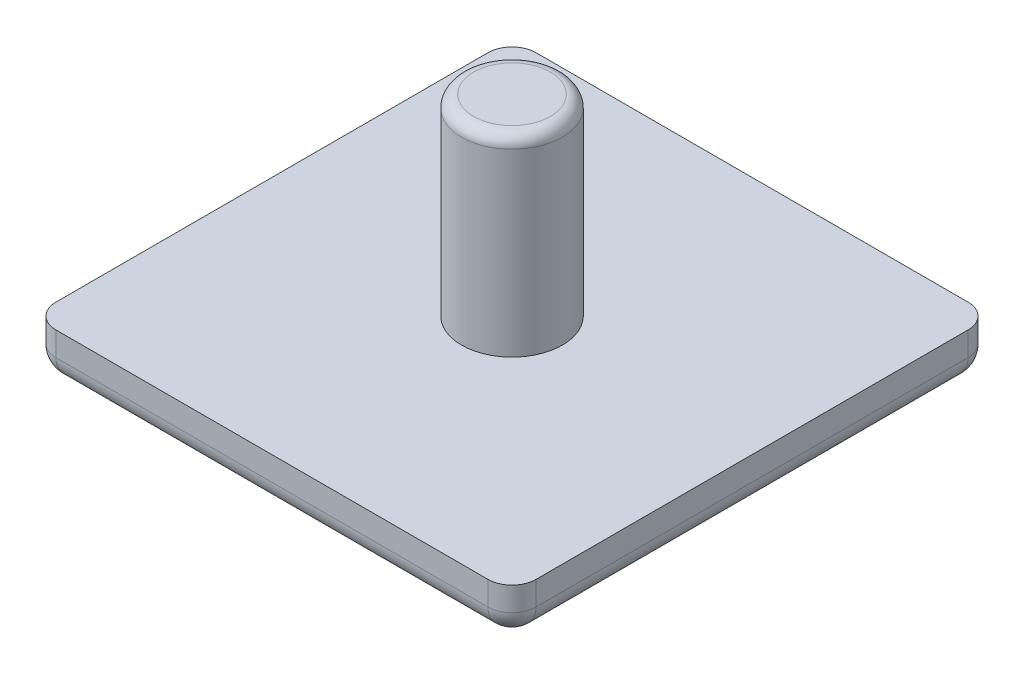
SolidWorks part; units mm, degrees
material "PVC Rigid"
ref_plane "Front Plane" through (0, 0, 0) normal (0, 0, 1) x (1, 0, 0)
ref_plane "Top Plane" through (0, 0, 0) normal (0, 1, 0) x (1, 0, 0)
ref_plane "Right Plane" through (0, 0, 0) normal (1, 0, 0) x (0, 0, -1)
sketch "Sketch1" plane through (0, 0, 0) normal (0, 1, 0) x (1, 0, 0)
  line L1 (0, 0) -> (20, 0)
  line L2 (0, 0) -> (0, 20)
  line L3 (0, 20) -> (20, 20)
  line L4 (20, 0) -> (20, 20)
  circle A0 centre (10, 10) radius 2.1
  point P8 (10, 0)
  point P10 (20, 10)
  dimension "D3" = 4.2
  dimension "D1" = 20
  dimension "D2" = 20
extrude "Boss-Extrude1" add sketch "Sketch1" along normal blind 8 contours A0
sketch "Sketch2" plane through (0, 0, 0) normal (0, -1, 0) x (1, 0, 0)
  line L1 (0, 0) -> (20, 0)
  line L2 (0, 0) -> (0, -20)
  line L3 (0, -20) -> (20, -20)
  line L4 (20, 0) -> (20, -20)
extrude "Boss-Extrude2" add sketch "Sketch2" along normal blind 2
fillet "Fillet1" radius 1 4 edges at (10, -2, 0) (20, -2, -10) (10, -2, -20) (0, -2, -10)
fillet "Fillet2" radius 0.5 1 edges at (10, 8, -7.9)
fillet "Fillet3" radius 1 8 edges at (0.2929, -1.7071, -0.2929) (0.2929, -1.7071, -19.7071) (19.7071, -1.7071, -19.7071) (19.7071, -1.7071, -0.2929) (0, -0.5, 0) (0, -0.5, -20) (20, -0.5, -20) (20, -0.5, 0)
